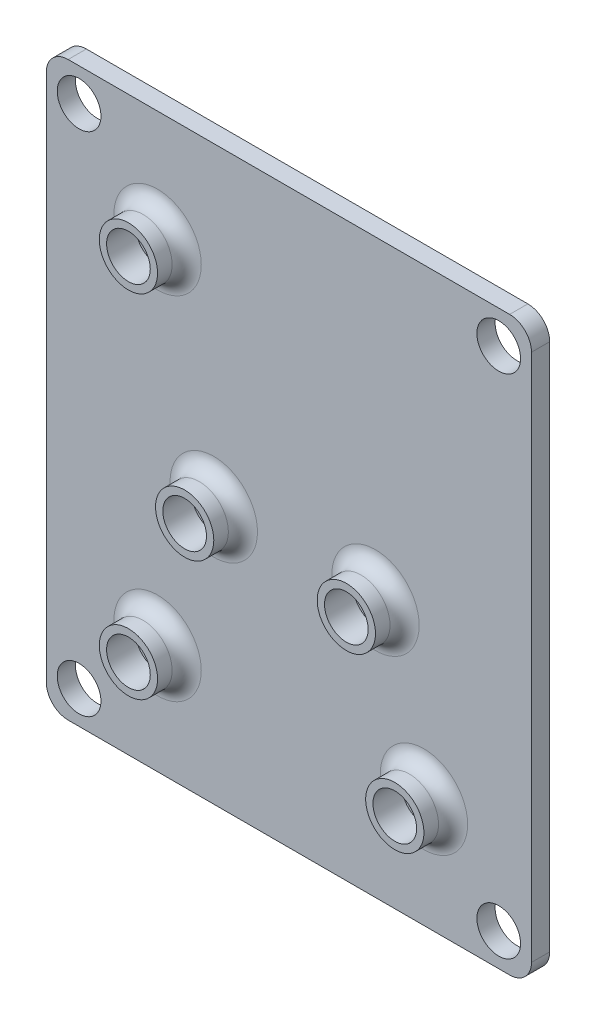
SolidWorks part; units mm, degrees
material "ABS"
ref_plane "Front Plane" through (0, 0, 0) normal (0, 0, 1) x (1, 0, 0)
ref_plane "Top Plane" through (0, 0, 0) normal (0, 1, 0) x (1, 0, 0)
ref_plane "Right Plane" through (0, 0, 0) normal (1, 0, 0) x (0, 0, -1)
sketch "Sketch1" plane through (0, 0, 0) normal (0, 0, 1) x (1, 0, 0)
  line L0 (12.065, 30.099) -> (12.065, 34.69) construction
  line L1 (0, 0) -> (24.13, 0) construction
  line L2 (0, 0) -> (0, 30.099) construction
  line L3 (0, 30.099) -> (24.13, 30.099) construction
  line L4 (24.13, 0) -> (24.13, 30.099) construction
  line L5 (-4.591, -4.591) -> (28.721, -4.591)
  line L6 (-4.591, -4.591) -> (-4.591, 34.69)
  line L7 (-4.591, 34.69) -> (28.721, 34.69)
  line L8 (28.721, -4.591) -> (28.721, 34.69)
  line L9 (12.065, -4.591) -> (12.065, 0) construction
  line L10 (-4.591, 15.0495) -> (0, 15.0495) construction
  line L11 (28.721, 15.0495) -> (24.13, 15.0495) construction
  line L12 (0, 0) -> (-4.591, 0) construction
  line L13 (0, 0) -> (0, -4.591) construction
  line L14 (-4.591, -4.591) -> (-3.4017, -3.4017) construction
  line L15 (-0.75, 15.0495) -> (0, 15.0495) construction
  line L16 (-1.2803, -1.2803) -> (-3.4017, -3.4017) construction
  line L17 (-3.841, -2.341) -> (-4.591, -2.341) construction
  line L18 (-0.75, -0.75) -> (24.88, -0.75)
  line L19 (-0.75, -0.75) -> (-0.75, 30.849)
  line L20 (-0.75, 30.849) -> (24.88, 30.849)
  line L21 (24.88, -0.75) -> (24.88, 30.849)
  line L22 (24.88, 15.0495) -> (24.13, 15.0495) construction
  line L23 (12.065, 30.849) -> (12.065, 30.099) construction
  line L24 (12.065, -0.75) -> (12.065, 0) construction
  line L25 (-1.2803, -1.2803) -> (-0.75, -0.75)
  line L27 (11.1079, 11.8549) -> (13.6479, 11.8549) construction
  line L28 (11.1079, 11.8549) -> (11.1079, 14.3949) construction
  line L29 (11.1079, 14.3949) -> (13.6479, 14.3949) construction
  line L30 (13.6479, 11.8549) -> (13.6479, 14.3949) construction
  circle A0 centre (3.048, 2.921) radius 1.5
  circle A1 centre (21.336, 2.921) radius 1.5
  circle A2 centre (3.048, 27.051) radius 1.5
  circle A3 centre (6.908, 13.095) radius 1.5
  circle A4 centre (18.0081, 13.095) radius 1.5
  circle A5 centre (-2.341, -2.341) radius 1.5
  circle A6 centre (26.471, -2.341) radius 1.5
  circle A7 centre (-2.341, 32.44) radius 1.5
  circle A8 centre (26.471, 32.44) radius 1.5
  circle A9 centre (3.048, 2.921) radius 2
  circle A10 centre (6.908, 13.095) radius 2
  circle A11 centre (18.0081, 13.095) radius 2
  circle A12 centre (21.336, 2.921) radius 2
  circle A13 centre (3.048, 27.051) radius 2
  circle A14 centre (11.1079, 14.3949) radius 1
  circle A15 centre (13.6479, 14.3949) radius 1
  circle A16 centre (11.1079, 11.8549) radius 1
  circle A17 centre (13.6479, 11.8549) radius 1
  dimension "D5" = 3
  dimension "D10" = 3
  dimension "D13" = 3
  dimension "D16" = 3
  dimension "D17" = 3
  dimension "D20" = 4
  dimension "D25" = 2
  dimension "D1" = 24.13
  dimension "D2" = 30.099
  dimension "D3" = 3.048
  dimension "D4" = 2.921
  dimension "D6" = 21.336
  dimension "D7" = 2.921
  dimension "D8" = 3.048
  dimension "D9" = 27.051
  dimension "D11" = 13.095
  dimension "D12" = 6.908
  dimension "D14" = 18.0081
  dimension "D15" = 13.095
  dimension "D18" = 0.75
  dimension "D19" = 0.75
  dimension "D21" = 11.1079
  dimension "D22" = 11.8549
  dimension "D23" = 13.6479
  dimension "D24" = 14.3949
extrude "Boss-Extrude1" add sketch "Sketch1" against normal blind 1.25 contours L18 L21 L20 L19 A17 A16 A15 A14 A13 A12 A11 A10 A9 | L5 L8 L7 L6 A8 A6 A5 L19 L20 L21 L18 A7 | A10 A3 | A11 A4 | A9 A0 | A12 A1 | A13 A2 | A3 | A4 | A1 | A0 | A2 | A14 | A15 | A17 | A16 region at (-4.0759, 15.0495, 0) region at (12.1961, 15.359, 0) region at (3.048, 2.921, 0) region at (21.336, 2.921, 0) region at (3.048, 27.051, 0) region at (6.908, 13.095, 0) region at (18.0081, 13.095, 0) region at (1.1046, 2.921, 0) region at (4.9646, 13.095, 0) region at (16.0647, 13.095, 0) region at (19.3926, 2.921, 0) region at (1.1046, 27.051, 0) region at (11.1079, 14.3949, 0) region at (13.6479, 14.3949, 0) region at (11.1079, 11.8549, 0) region at (13.6479, 11.8549, 0)
fillet "Fillet1" radius 1.5 4 edges at (-4.591, -4.591, -0.625) (-4.591, 34.69, -0.625) (28.721, 34.69, -0.625) (28.721, -4.591, -0.625)
extrude "Boss-Extrude2" add sketch "Sketch1<16>" along normal blind 2 contours A13 A2 | A10 A3 | A11 A4 | A12 A1 | A9 A0 region at (1.1046, 2.921, 0) region at (4.9646, 13.095, 0) region at (16.0647, 13.095, 0) region at (19.3926, 2.921, 0) region at (1.1046, 27.051, 0)
sketch "Sketch1<16>" plane through (0, 0, 0) normal (0, 0, 1) x (1, 0, 0) same geometry as "Sketch1"
fillet "Fillet2" radius 1 5 edges at (5.048, 2.921, 0) (23.336, 2.921, 0) (20.0081, 13.095, 0) (8.908, 13.095, 0) (5.048, 27.051, 0)
